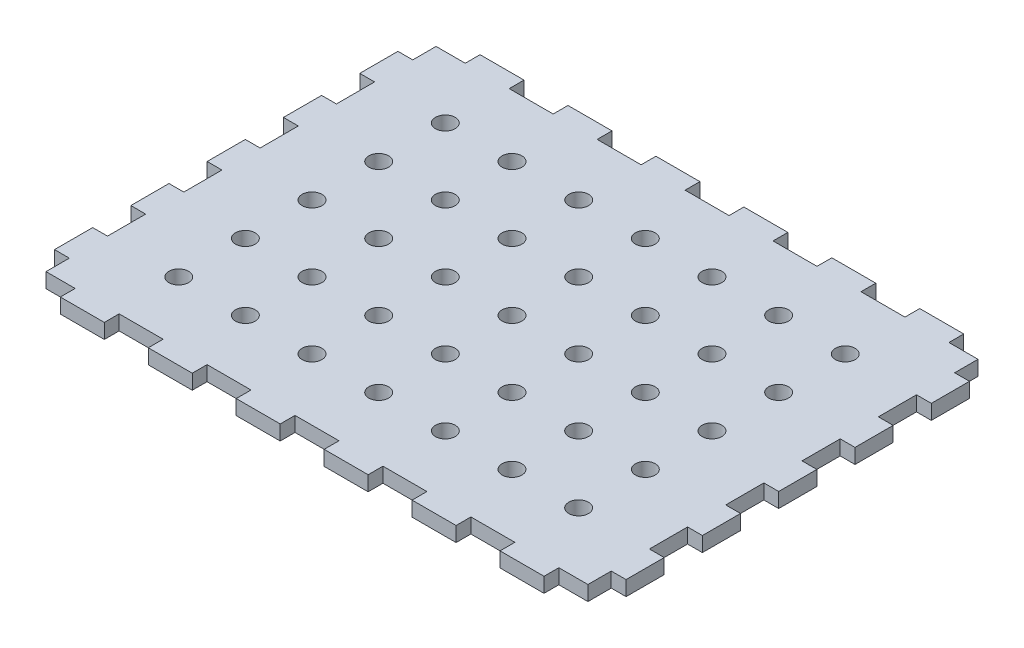
SolidWorks part; units mm, degrees
material "Balsa"
ref_plane "Front" through (0, 0, 0) normal (0, 0, 1) x (1, 0, 0)
ref_plane "Top" through (0, 0, 0) normal (0, 1, 0) x (1, 0, 0)
ref_plane "Right" through (0, 0, 0) normal (1, 0, 0) x (0, 0, -1)
sketch "Esboço1" plane through (0, 0, 0) normal (0, 1, 0) x (1, 0, 0)
  line L0 (-115.75, 85) -> (-97.75, 85) construction
  line L1 (115.75, -85) -> (-115.75, -85)
  line L2 (115.75, -85) -> (115.75, 85)
  line L3 (115.75, 85) -> (-115.75, 85)
  line L4 (-115.75, -85) -> (-115.75, 85)
  line L5 (115.75, -85) -> (-115.75, 85) construction
  line L6 (115.75, 85) -> (-115.75, -85) construction
  line L7 (-97.75, 85) -> (-97.75, 67) construction
  line L8 (-97.75, 67) -> (-115.75, 67) construction
  line L9 (115.75, -85) -> (97.75, -85) construction
  line L10 (97.75, -85) -> (97.75, -67) construction
  line L11 (97.75, -67) -> (115.75, -67) construction
  line L12 (-97.75, 67) -> (-97.75, 54) construction
  line L13 (-97.75, 67) -> (97.75, 67)
  line L14 (-97.75, 67) -> (-97.75, -67)
  line L15 (-97.75, -67) -> (97.75, -67)
  line L16 (97.75, 67) -> (97.75, -67)
  line L17 (-97.75, 54) -> (-81, 54) construction
  circle A0 centre (-81, 54) radius 4
  circle A1 centre (-54, 54) radius 4
  circle A2 centre (-27, 54) radius 4
  circle A3 centre (0, 54) radius 4
  circle A4 centre (27, 54) radius 4
  circle A5 centre (54, 54) radius 4
  circle A6 centre (81, 54) radius 4
  circle A7 centre (-54, 27) radius 4
  circle A8 centre (-27, 27) radius 4
  circle A9 centre (0, 27) radius 4
  circle A10 centre (27, 27) radius 4
  circle A11 centre (54, 27) radius 4
  circle A12 centre (81, 27) radius 4
  circle A13 centre (-54, 0) radius 4
  circle A14 centre (-27, 0) radius 4
  circle A15 centre (0, 0) radius 4
  circle A16 centre (27, 0) radius 4
  circle A17 centre (54, 0) radius 4
  circle A18 centre (81, 0) radius 4
  circle A19 centre (-54, -27) radius 4
  circle A20 centre (-27, -27) radius 4
  circle A21 centre (0, -27) radius 4
  circle A22 centre (27, -27) radius 4
  circle A23 centre (54, -27) radius 4
  circle A24 centre (81, -27) radius 4
  circle A25 centre (-54, -54) radius 4
  circle A26 centre (-27, -54) radius 4
  circle A27 centre (0, -54) radius 4
  circle A28 centre (27, -54) radius 4
  circle A29 centre (54, -54) radius 4
  circle A30 centre (81, -54) radius 4
  circle A31 centre (-81, 27) radius 4
  circle A32 centre (-81, 0) radius 4
  circle A33 centre (-81, -27) radius 4
  circle A34 centre (-81, -54) radius 4
  point P0 (0, 0)
  dimension "D7" = 7
  dimension "D1" = 231.5
  dimension "D2" = 170
  dimension "D3" = 195.5
  dimension "D4" = 134
  dimension "D5" = 13
  dimension "D6" = 16.75
  dimension "D8" = 5
extrude "Ressalto-extrusão1" add sketch "Esboço1" along normal blind 6 contours L16 L13 L14 L15 A34 A33 A32 A31 A30 A29 A28 A27 A26 A25 A24 A23 A22 A21 A20 A19 A18 A17 A16 A15 A14 A13 A12 | L4 L1 L2 L3 L13 L16 L15 L14 region at (0, 0, 82.1279) region at (0, 0, -64.6298)
sketch "Esboço5" plane through (0, 0, 0) normal (0, 1, 0) x (1, 0, 0)
  line L0 (-115.75, 85) -> (-97.75, 85) construction
  line L1 (115.75, -85) -> (-115.75, -85)
  line L2 (115.75, -85) -> (115.75, 85)
  line L3 (115.75, 85) -> (-115.75, 85)
  line L4 (-115.75, -85) -> (-115.75, 85)
  line L5 (115.75, -85) -> (-115.75, 85) construction
  line L6 (115.75, 85) -> (-115.75, -85) construction
  line L7 (-97.75, 85) -> (-97.75, 67) construction
  line L8 (-97.75, 67) -> (-115.75, 67) construction
  line L9 (115.75, -85) -> (97.75, -85) construction
  line L10 (97.75, -85) -> (97.75, -67) construction
  line L11 (97.75, -67) -> (115.75, -67) construction
  line L12 (-97.75, 67) -> (-97.75, 54) construction
  line L13 (-97.75, 67) -> (97.75, 67)
  line L14 (-97.75, 67) -> (-97.75, -67)
  line L15 (-97.75, -67) -> (97.75, -67)
  line L16 (97.75, 67) -> (97.75, -67)
  line L17 (-97.75, 54) -> (-81, 54) construction
  circle A0 centre (-81, 54) radius 4
  circle A1 centre (-54, 54) radius 4
  circle A2 centre (-27, 54) radius 4
  circle A3 centre (0, 54) radius 4
  circle A4 centre (27, 54) radius 4
  circle A5 centre (54, 54) radius 4
  circle A6 centre (81, 54) radius 4
  circle A7 centre (-54, 27) radius 4
  circle A8 centre (-27, 27) radius 4
  circle A9 centre (0, 27) radius 4
  circle A10 centre (27, 27) radius 4
  circle A11 centre (54, 27) radius 4
  circle A12 centre (81, 27) radius 4
  circle A13 centre (-54, 0) radius 4
  circle A14 centre (-27, 0) radius 4
  circle A15 centre (0, 0) radius 4
  circle A16 centre (27, 0) radius 4
  circle A17 centre (54, 0) radius 4
  circle A18 centre (81, 0) radius 4
  circle A19 centre (-54, -27) radius 4
  circle A20 centre (-27, -27) radius 4
  circle A21 centre (0, -27) radius 4
  circle A22 centre (27, -27) radius 4
  circle A23 centre (54, -27) radius 4
  circle A24 centre (81, -27) radius 4
  circle A25 centre (-54, -54) radius 4
  circle A26 centre (-27, -54) radius 4
  circle A27 centre (0, -54) radius 4
  circle A28 centre (27, -54) radius 4
  circle A29 centre (54, -54) radius 4
  circle A30 centre (81, -54) radius 4
  circle A31 centre (-81, 27) radius 4
  circle A32 centre (-81, 0) radius 4
  circle A33 centre (-81, -27) radius 4
  circle A34 centre (-81, -54) radius 4
  point P0 (0, 0)
  dimension "D7" = 7
  dimension "D1" = 231.5
  dimension "D2" = 170
  dimension "D3" = 195.5
  dimension "D4" = 134
  dimension "D5" = 13
  dimension "D6" = 16.75
  dimension "D8" = 5
sketch "Esboço6" plane through (0, 0, 0) normal (0, -1, 0) x (1, 0, 0)
  line L0 (115.75, 85) -> (-115.75, 85) construction
  line L1 (-115.75, 85) -> (-97.9423, 85)
  line L2 (-80.13, 85) -> (-62.3223, 85)
  line L3 (-115.75, 85) -> (-97.9423, 85)
  line L4 (-115.75, 85) -> (-115.75, 79)
  line L5 (-115.75, 79) -> (-97.9423, 79)
  line L6 (-97.9423, 85) -> (-97.9423, 79)
  line L7 (-80.13, 85) -> (-62.3223, 85)
  line L8 (-80.13, 85) -> (-80.13, 79)
  line L9 (-80.13, 79) -> (-62.3223, 79)
  line L10 (-62.3223, 85) -> (-62.3223, 79)
  line L11 (-44.51, 85) -> (-26.7023, 85)
  line L12 (-44.51, 85) -> (-26.7023, 85)
  line L13 (-44.51, 85) -> (-44.51, 79)
  line L14 (-44.51, 79) -> (-26.7023, 79)
  line L15 (-26.7023, 85) -> (-26.7023, 79)
  line L16 (-8.89, 85) -> (8.9177, 85)
  line L17 (-8.89, 85) -> (8.9177, 85)
  line L18 (-8.89, 85) -> (-8.89, 79)
  line L19 (-8.89, 79) -> (8.9177, 79)
  line L20 (8.9177, 85) -> (8.9177, 79)
  line L21 (26.73, 85) -> (44.5377, 85)
  line L22 (26.73, 85) -> (44.5377, 85)
  line L23 (26.73, 85) -> (26.73, 79)
  line L24 (26.73, 79) -> (44.5377, 79)
  line L25 (44.5377, 85) -> (44.5377, 79)
  line L26 (62.35, 85) -> (80.1577, 85)
  line L27 (62.35, 85) -> (80.1577, 85)
  line L28 (62.35, 85) -> (62.35, 79)
  line L29 (62.35, 79) -> (80.1577, 79)
  line L30 (80.1577, 85) -> (80.1577, 79)
  line L31 (97.97, 85) -> (115.7777, 85)
  line L32 (97.97, 85) -> (115.7777, 85)
  line L33 (97.97, 85) -> (97.97, 79)
  line L34 (97.97, 79) -> (115.7777, 79)
  line L35 (115.7777, 85) -> (115.7777, 79)
  line L37 (-115.75, -79) -> (-97.9423, -79)
  line L38 (-80.13, -79) -> (-62.3223, -79)
  line L39 (-115.75, -79) -> (-97.9423, -79)
  line L40 (-115.75, -79) -> (-115.75, -85)
  line L41 (-115.75, -85) -> (-97.9423, -85)
  line L42 (-97.9423, -79) -> (-97.9423, -85)
  line L43 (-80.13, -79) -> (-62.3223, -79)
  line L44 (-80.13, -79) -> (-80.13, -85)
  line L45 (-80.13, -85) -> (-62.3223, -85)
  line L46 (-62.3223, -79) -> (-62.3223, -85)
  line L47 (-44.51, -79) -> (-26.7023, -79)
  line L48 (-44.51, -79) -> (-26.7023, -79)
  line L49 (-44.51, -79) -> (-44.51, -85)
  line L50 (-44.51, -85) -> (-26.7023, -85)
  line L51 (-26.7023, -79) -> (-26.7023, -85)
  line L52 (-8.89, -79) -> (8.9177, -79)
  line L53 (-8.89, -79) -> (8.9177, -79)
  line L54 (-8.89, -79) -> (-8.89, -85)
  line L55 (-8.89, -85) -> (8.9177, -85)
  line L56 (8.9177, -79) -> (8.9177, -85)
  line L57 (26.73, -79) -> (44.5377, -79)
  line L58 (26.73, -79) -> (44.5377, -79)
  line L59 (26.73, -79) -> (26.73, -85)
  line L60 (26.73, -85) -> (44.5377, -85)
  line L61 (44.5377, -79) -> (44.5377, -85)
  line L62 (62.35, -79) -> (80.1577, -79)
  line L63 (62.35, -79) -> (80.1577, -79)
  line L64 (62.35, -79) -> (62.35, -85)
  line L65 (62.35, -85) -> (80.1577, -85)
  line L66 (80.1577, -79) -> (80.1577, -85)
  line L67 (97.97, -79) -> (115.7777, -79)
  line L68 (97.97, -79) -> (115.7777, -79)
  line L69 (97.97, -79) -> (97.97, -85)
  line L70 (97.97, -85) -> (115.7777, -85)
  line L71 (115.7777, -79) -> (115.7777, -85)
  line M109 (-115.75, 85) -> (-115.75, -85)
  line M110 (-115.75, -85) -> (115.75, -85)
  line M111 (115.75, -85) -> (115.75, 85)
  line M112 (115.75, 85) -> (-115.75, 85)
  dimension "D1" = 17.8077
  dimension "D2" = 6
  dimension "D4" = 2
  dimension "D3" = 7
extrude "Corte-extrusão1" cut sketch "Esboço6" against normal blind 6 contours L6 L5 M112 M109 | L10 L8 L9 M112 | L15 L13 L14 M112 | L20 L18 L19 M112 | L25 L23 L24 M112 | L30 L28 L29 M112 | L33 L34 M111 M112 | L67 L69 M110 M111 | L66 L62 L64 M110 | L61 L57 L59 M110 | L56 L52 L54 M110 | L51 L47 L49 M110 | L46 L38 L44 M110 | L42 L37 M109 M110 region at (-106.8462, 0, 82) region at (-71.2262, 0, 82) region at (-106.8462, 0, -82) region at (-35.6062, 0, 82) region at (-71.2262, 0, -82) region at (0.0138, 0, 82) region at (-35.6062, 0, -82) region at (35.6338, 0, 82) region at (0.0138, 0, -82) region at (71.2538, 0, 82) region at (35.6338, 0, -82) region at (106.86, 0, 82) region at (71.2538, 0, -82) region at (106.86, 0, -82)
sketch "Esboço7" plane through (0, 0, 0) normal (0, -1, 0) x (1, 0, 0)
  line L0 (109.75, -85) -> (115.75, -85)
  line L1 (-115.75, -85) -> (-109.75, -85)
  line L2 (-115.75, -85) -> (-115.75, -69.5455)
  line L3 (-115.75, -69.5455) -> (-109.75, -69.5455)
  line L4 (-109.75, -85) -> (-109.75, -69.5455)
  line L5 (109.75, -85) -> (109.75, -69.5455)
  line L6 (109.75, -69.5455) -> (115.75, -69.5455)
  line L7 (115.75, -85) -> (115.75, -69.5455)
  line L8 (109.75, -54.09) -> (115.75, -54.09)
  line L9 (109.75, -54.09) -> (109.75, -38.6355)
  line L10 (109.75, -38.6355) -> (115.75, -38.6355)
  line L11 (115.75, -54.09) -> (115.75, -38.6355)
  line L12 (109.75, -23.18) -> (115.75, -23.18)
  line L13 (109.75, -23.18) -> (109.75, -7.7255)
  line L14 (109.75, -7.7255) -> (115.75, -7.7255)
  line L15 (115.75, -23.18) -> (115.75, -7.7255)
  line L16 (109.75, 7.73) -> (115.75, 7.73)
  line L17 (109.75, 7.73) -> (109.75, 23.1845)
  line L18 (109.75, 23.1845) -> (115.75, 23.1845)
  line L19 (115.75, 7.73) -> (115.75, 23.1845)
  line L20 (109.75, 38.64) -> (115.75, 38.64)
  line L21 (109.75, 38.64) -> (109.75, 54.0945)
  line L22 (109.75, 54.0945) -> (115.75, 54.0945)
  line L23 (115.75, 38.64) -> (115.75, 54.0945)
  line L24 (109.75, 69.55) -> (115.75, 69.55)
  line L25 (109.75, 69.55) -> (109.75, 85.0045)
  line L26 (109.75, 85.0045) -> (115.75, 85.0045)
  line L27 (115.75, 69.55) -> (115.75, 85.0045)
  line L28 (-115.75, -54.09) -> (-109.75, -54.09)
  line L29 (-115.75, -54.09) -> (-115.75, -38.6355)
  line L30 (-115.75, -38.6355) -> (-109.75, -38.6355)
  line L31 (-109.75, -54.09) -> (-109.75, -38.6355)
  line L32 (-115.75, -23.18) -> (-109.75, -23.18)
  line L33 (-115.75, -23.18) -> (-115.75, -7.7255)
  line L34 (-115.75, -7.7255) -> (-109.75, -7.7255)
  line L35 (-109.75, -23.18) -> (-109.75, -7.7255)
  line L36 (-115.75, 7.73) -> (-109.75, 7.73)
  line L37 (-115.75, 7.73) -> (-115.75, 23.1845)
  line L38 (-115.75, 23.1845) -> (-109.75, 23.1845)
  line L39 (-109.75, 7.73) -> (-109.75, 23.1845)
  line L40 (-115.75, 38.64) -> (-109.75, 38.64)
  line L41 (-115.75, 38.64) -> (-115.75, 54.0945)
  line L42 (-115.75, 54.0945) -> (-109.75, 54.0945)
  line L43 (-109.75, 38.64) -> (-109.75, 54.0945)
  line L44 (-115.75, 69.55) -> (-109.75, 69.55)
  line L45 (-115.75, 69.55) -> (-115.75, 85.0045)
  line L46 (-115.75, 85.0045) -> (-109.75, 85.0045)
  line L47 (-109.75, 69.55) -> (-109.75, 85.0045)
  dimension "D1" = 6
  dimension "D2" = 15.4545
  dimension "D3" = 2
  dimension "D4" = 6
extrude "Corte-extrusão2" cut sketch "Esboço7" against normal up to next
